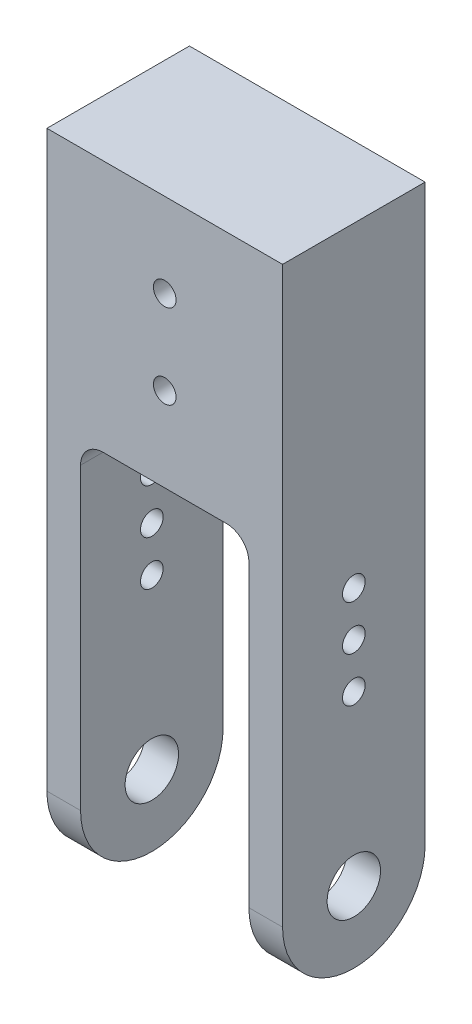
SolidWorks part; units mm, degrees
ref_plane "前基準面" through (0, 0, 0) normal (0, 0, 1) x (1, 0, 0)
ref_plane "上基準面" through (0, 0, 0) normal (0, 1, 0) x (1, 0, 0)
ref_plane "右基準面" through (0, 0, 0) normal (1, 0, 0) x (0, 0, -1)
sketch "草圖1" plane through (0, 0, 0) normal (0, 1, 0) x (1, 0, 0)
  line L1 (-21, -12.7) -> (21, -12.7)
  line L2 (-21, -12.7) -> (-21, 12.7)
  line L3 (-21, 12.7) -> (21, 12.7)
  line L4 (21, -12.7) -> (21, 12.7)
  line L5 (-21, -12.7) -> (21, 12.7) construction
  line L6 (-21, 12.7) -> (21, -12.7) construction
  point P0 (0, 0)
  dimension "D1" = 42
  dimension "D2" = 25.4
extrude "填料-伸長1" add sketch "草圖1" along normal blind 70
sketch "草圖2" plane through (21, 0, 0) normal (1, 0, 0) x (0, 0, -1)
  line L0 (0, 70) -> (0, 0) construction
  line L1 (-12.7, 70) -> (12.7, 70) construction
  line L2 (-12.7, 0) -> (12.7, 0) construction
  line L3 (-8.75, 70) -> (-8.75, 0)
  line L4 (-8.75, 70) -> (8.75, 70)
  line L5 (-8.75, 0) -> (8.75, 0)
  line L6 (8.75, 70) -> (8.75, 0)
  line L7 (-8.75, 70) -> (8.75, 0) construction
  line L8 (-8.75, 0) -> (8.75, 70) construction
  point P6 (0, 35)
  point P8 (0, 35)
  dimension "D1" = 17.5
sketch "草圖3" plane through (-21, 0, 0) normal (-1, 0, 0) x (0, 0, 1)
  line L0 (0, 0) -> (0, 70) construction
  line L1 (-12.7, 0) -> (12.7, 0) construction
  line L2 (-12.7, 70) -> (12.7, 70) construction
  line L3 (8.75, 70) -> (8.75, 0)
  line L4 (8.75, 70) -> (-8.75, 70)
  line L5 (8.75, 0) -> (-8.75, 0)
  line L6 (-8.75, 70) -> (-8.75, 0)
  line L7 (8.75, 70) -> (-8.75, 0) construction
  line L8 (8.75, 0) -> (-8.75, 70) construction
  point P6 (0, 35)
  point P8 (0, 35)
  dimension "D1" = 17.5
sketch "草圖5" plane through (0, 0, 0) normal (0, -1, 0) x (1, 0, 0)
  line L0 (21, -12.7) -> (-21, -12.7) construction
  line L1 (-21, 12.7) -> (-15, 12.7)
  line L2 (-21, 12.7) -> (-21, -12.7)
  line L3 (-21, -12.7) -> (-15, -12.7)
  line L4 (-15, 12.7) -> (-15, -12.7)
  line L6 (21, 12.7) -> (15, 12.7)
  line L7 (21, 12.7) -> (21, -12.7)
  line L8 (21, -12.7) -> (15, -12.7)
  line L9 (15, 12.7) -> (15, -12.7)
  dimension "D1" = 6
  dimension "D2" = 6
extrude "填料-伸長5" add sketch "草圖5" along normal blind 70
sketch "草圖6" plane through (-21, 0, 0) normal (-1, 0, 0) x (0, 0, 1)
  line L0 (0, -70) -> (0, 70) construction
  line L2 (12.7, -70) -> (-12.7, -70) construction
  line L3 (-12.7, 70) -> (12.7, 70) construction
  circle A0 centre (0, -57.3) radius 4.7625
  dimension "D1" = 9.525
  dimension "D2" = 12.7
extrude "除料-伸長2" cut sketch "草圖6" against normal through all
fillet "圓角6" radius 4 2 edges at (15, 0, 0)
hole_wizard "#10-32 螺紋孔1" positions "草圖8" profile "草圖7" tap size "#10-32" standard "Ansi 英吋" end condition through all
sketch "草圖8" plane through (0, 0, 12.7) normal (0, 0, 1) x (1, 0, 0)
  line L0 (0, 70) -> (0, 0) construction
  line L1 (-21, 70) -> (21, 70) construction
  line L2 (-11, 0) -> (11, 0) construction
  point P0 (0, 30)
  point P11 (0, 15)
  dimension "D1" = 30
  dimension "D2" = 15
cosmetic thread "鑽孔螺紋1" parameters "D2"=4.826
cosmetic thread "鑽孔螺紋2" parameters "D2"=4.826
sketch "草圖7" plane through (0, 30, 12.7) normal (1, 0, 0) x (0, -1, 0)
  line L0 (0, 0) -> (0, 25.4)
  line L1 (0, 25.4) -> (2.0193, 25.4)
  line L2 (2.0193, 25.4) -> (2.0193, 0)
  line L5 (2.0193, 0) -> (0, 0)
  line L11 (0, -6.35) -> (0, 107.95) construction
  dimension "貫穿螺孔鑽直徑" = 4.0386
  dimension "貫穿螺孔鑽深度" = 25.4
fillet "圓角7" radius 12.7 4 edges at (18, -70, 12.7) (18, -70, -12.7) (-18, -70, 12.7) (-18, -70, -12.7)
sketch "草圖9" plane through (0, 0, 12.7) normal (0, 0, 1) x (1, 0, 0)
  line L0 (-21, 70) -> (-21, -57.3) construction
  line L1 (21, 70) -> (-21, 70)
  line L2 (21, 70) -> (21, 45)
  line L3 (21, 45) -> (-21, 45)
  line L4 (-21, 70) -> (-21, 45)
  circle A0 centre (0, 30) radius 2.0193 construction
  dimension "D1" = 15
extrude "除料-伸長3" cut sketch "草圖9" against normal through all
hole_wizard "#10-32 螺紋孔2" positions "草圖11" profile "草圖10" tap size "#10-32" standard "Ansi 英吋" end condition through all
sketch "草圖11" plane through (21, 0, 0) normal (1, 0, 0) x (0, 0, -1)
  line L0 (0, -57.3) -> (0, 17.6153) construction
  point P0 (0, -11.3)
  point P10 (0, -19.3)
  point P12 (0, -27.3)
  dimension "D1" = 30
  dimension "D2" = 38
  dimension "D3" = 46
sketch "草圖10" plane through (21, -11.3, 0) normal (0, 1, 0) x (0, 0, -1)
  line L0 (0, 0) -> (0, 42)
  line L1 (0, 42) -> (2.0193, 42)
  line L2 (2.0193, 42) -> (2.0193, 0)
  line L5 (2.0193, 0) -> (0, 0)
  line L11 (0, -6.35) -> (0, 107.95) construction
  dimension "貫穿螺孔鑽直徑" = 4.0386
  dimension "貫穿螺孔鑽深度" = 42
cosmetic thread "鑽孔螺紋3" parameters "D2"=4.826
cosmetic thread "鑽孔螺紋4" parameters "D2"=4.826
cosmetic thread "鑽孔螺紋5" parameters "D2"=4.826
